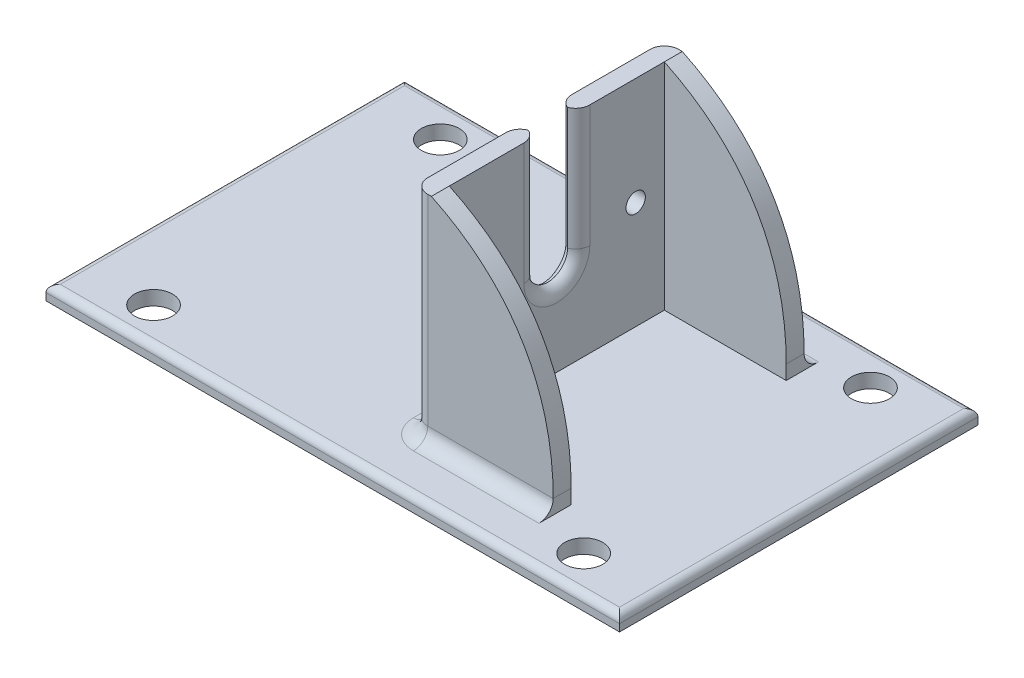
SolidWorks part; units mm, degrees
ref_plane "前视基准面" through (0, 0, 0) normal (0, 0, 1) x (1, 0, 0)
ref_plane "上视基准面" through (0, 0, 0) normal (0, 1, 0) x (1, 0, 0)
ref_plane "右视基准面" through (0, 0, 0) normal (1, 0, 0) x (0, 0, -1)
other "Configuration Table"
sketch "草图2" plane through (0, 0, 0) normal (0, 1, 0) x (1, 0, 0)
  line L0 (0, 37.2969) -> (0, -30.696) construction
  line L1 (-40, -25) -> (40, -25)
  line L2 (-40, -25) -> (-40, 25)
  line L3 (-40, 25) -> (40, 25)
  line L4 (40, -25) -> (40, 25)
  line L5 (-40, -25) -> (40, 25) construction
  line L6 (-40, 25) -> (40, -25) construction
  line L7 (-46.1505, 0) -> (56.6491, 0) construction
  circle A0 centre (-30, 20) radius 2.65
  circle A1 centre (30, 20) radius 2.65
  circle A2 centre (-30, -20) radius 2.65
  circle A3 centre (30, -20) radius 2.65
  point P0 (0, 0)
  dimension "D5" = 5.3
  dimension "D1" = 80
  dimension "D2" = 50
  dimension "D3" = 5
  dimension "D4" = 10
extrude "凸台-拉伸1" add sketch "草图2" along normal blind 2
sketch "草图3" plane through (0, 2, 0) normal (0, 1, 0) x (1, 0, 0)
  line L0 (-40.7797, 0) -> (42.7848, 0) construction
  line L1 (3.75, -17.5) -> (6.25, -17.5)
  line L2 (3.75, -17.5) -> (3.75, 17.5)
  line L3 (3.75, 17.5) -> (6.25, 17.5)
  line L4 (6.25, -17.5) -> (6.25, 17.5)
  line L5 (3.75, -17.5) -> (6.25, 17.5) construction
  line L6 (3.75, 17.5) -> (6.25, -17.5) construction
  line L7 (6.25, 17.5) -> (23.25, 17.5)
  line L8 (6.25, 17.5) -> (6.25, 15)
  line L9 (6.25, 15) -> (23.25, 15)
  line L10 (23.25, 17.5) -> (23.25, 15)
  line L11 (23.25, -17.5) -> (23.25, -15)
  line L12 (6.25, -15) -> (23.25, -15)
  line L13 (6.25, -17.5) -> (6.25, -15)
  line L14 (6.25, -17.5) -> (23.25, -17.5)
  point P0 (5, 0)
  dimension "D1" = 2.5
  dimension "D2" = 35
  dimension "D3" = 2.5
  dimension "D4" = 17
  dimension "D5" = 5
extrude "凸台-拉伸2" add sketch "草图3" along normal blind 30 contours L1 L4 L3 L2 | L10 L7 L4 L9 | L4 L14 L11 L12 region at (5, 2, 0) region at (14.75, 2, 16.25) region at (14.75, 2, -16.25)
sketch "草图4" plane through (3.75, 0, 0) normal (-1, 0, 0) x (0, 0, 1)
  line L0 (17.5, 32) -> (-17.5, 32) construction
  line L1 (-2.6, 15) -> (2.6, 15)
  line L2 (-2.6, 15) -> (-2.6, 32)
  line L3 (-2.6, 32) -> (2.6, 32)
  line L4 (2.6, 15) -> (2.6, 32)
  line L5 (-2.6, 15) -> (2.6, 32) construction
  line L6 (-2.6, 32) -> (2.6, 15) construction
  line L7 (-17.5, 32) -> (-17.5, 2) construction
  line L8 (-25, 2) -> (25, 2) construction
  line L9 (0, 34.3416) -> (0, -5.9893) construction
  arc A0 (-2.6, 15) -> (2.6, 15) centre (0, 15) ccw
  circle A1 centre (-11, 17) radius 1.35
  circle A2 centre (11, 17) radius 1.35
  point P0 (0, 23.5)
  line M6 (17.5, 32) -> (-17.5, 32)
  dimension "D3" = 2.7
  dimension "D1" = 5.2
  dimension "D2" = 17
  dimension "D4" = 6.5
  dimension "D5" = 15
extrude "切除-拉伸1" cut sketch "草图4" against normal up to next contours A2 | A1 | L1 L4 L2 M6 | L1 A0 region at (3.75, 23.5, 0) region at (3.75, 13.8965, 0) region at (3.75, 17, -11) region at (3.75, 17, 11)
fillet "圆角1" radius 2 11 edges at (13.5, 2, 17.5) (6.25, 23.5, 2.6) (6.25, 23.5, -2.6) (3.75, 23.5, -2.6) (3.75, 23.5, 2.6) (6.25, 12.4, 0) (3.75, 12.4, 0) (3.75, 17, -17.5) (13.5, 2, -17.5) (3.75, 2, 0) (3.75, 17, 17.5)
fillet "圆角2" radius 1 4 edges at (40, 2, 0) (0, 2, -25) (-40, 2, 0) (0, 2, 25)
sketch "草图5" plane through (0, 0, 17.5) normal (0, 0, 1) x (1, 0, 0)
  line L5 (5.75, 32) -> (23.25, 32) construction
  line L7 (5.75, 32) -> (23.25, 32)
  line L8 (23.25, 32) -> (23.25, 4) construction
  line L9 (23.25, 32) -> (23.25, 4)
  spline S0 degree 3 poles (6.25, 32) (16.535, 27.0887) (23.25, 17.8814) (23.25, 4) knots 0 0 0 0 1 1 1 1
  point P2 (14.6194, 26.2536)
  point P4 (0, 0)
  point P10 (6.3253, 32)
  line M6 (23.25, 4) -> (23.25, 32)
  line M7 (23.25, 32) -> (5.75, 32)
extrude "切除-拉伸2" cut sketch "草图5" against normal through all contours S0 M7 M6 region at (18.5964, 25.7263, 17.5)
